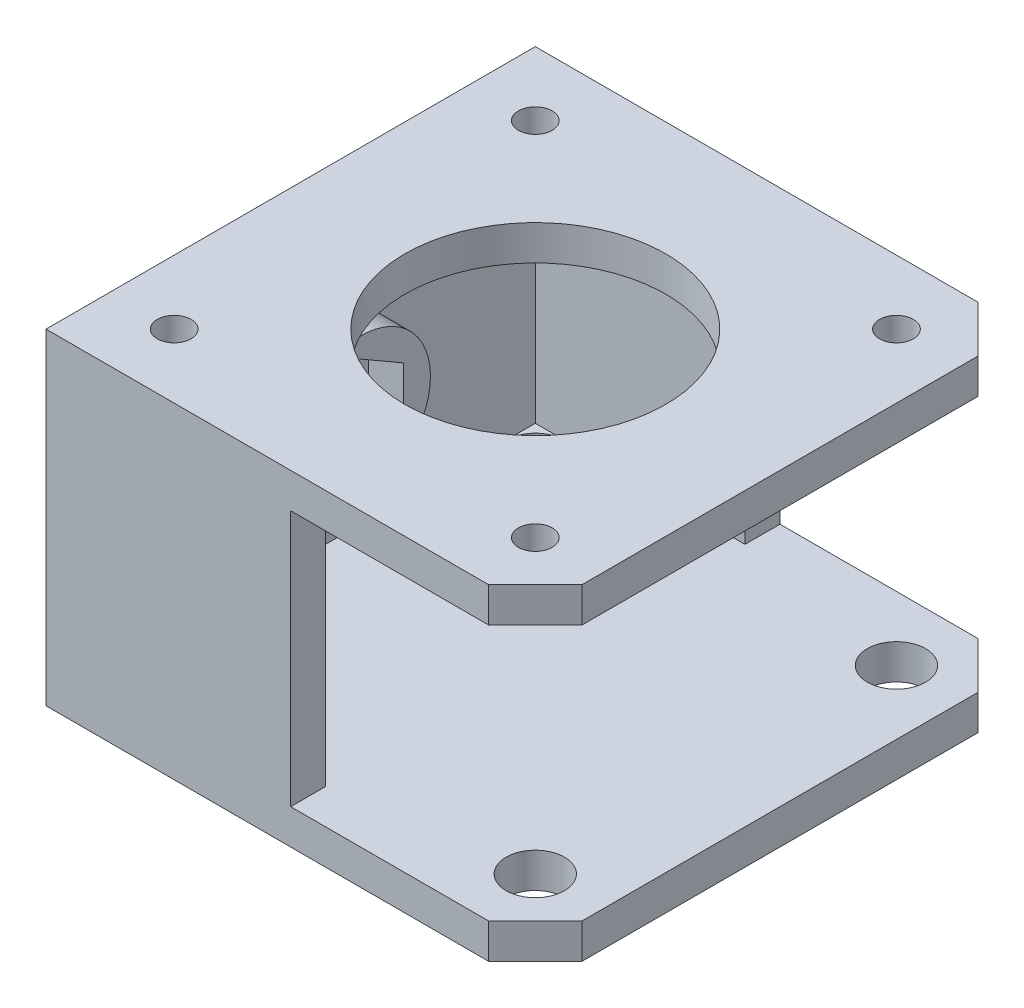
SolidWorks part; units mm, degrees
ref_plane "Front Plane" through (0, 0, 0) normal (0, 0, 1) x (1, 0, 0)
ref_plane "Top Plane" through (0, 0, 0) normal (0, 1, 0) x (1, 0, 0)
ref_plane "Right Plane" through (0, 0, 0) normal (1, 0, 0) x (0, 0, -1)
sketch "Sketch1" plane through (0, 0, 0) normal (0, 1, 0) x (1, 0, 0)
  line L0 (0, 21) -> (0, 18)
  line L1 (-21, -21) -> (21, -21)
  line L2 (-21, -21) -> (-21, 21)
  line L3 (-21, 21) -> (21, 21)
  line L4 (21, -21) -> (21, 21)
  line L5 (-21, -21) -> (21, 21) construction
  line L6 (-21, 21) -> (21, -21) construction
  line L7 (-18, -18) -> (18, -18)
  line L8 (-18, -18) -> (-18, 18)
  line L9 (-18, 18) -> (18, 18)
  line L10 (18, -18) -> (18, 18)
  line L11 (-18, -18) -> (18, 18) construction
  line L12 (-18, 18) -> (18, -18) construction
  line L13 (0, -18) -> (0, -21)
  circle A0 centre (0, 0) radius 11.2
  circle A1 centre (-15.5, 15.5) radius 1.45
  circle A2 centre (15.5, 15.5) radius 1.45
  circle A3 centre (15.5, -15.5) radius 1.45
  circle A4 centre (-15.5, -15.5) radius 1.45
  point P0 (0, 0)
  point P6 (0, 0)
  point P24 (0, 0)
  dimension "D3" = 22.4
  dimension "D4" = 2.9
  dimension "D1" = 42
  dimension "D2" = 3
  dimension "D6" = 31
  dimension "D5" = 4
extrude "Boss-Extrude1" add sketch "Sketch1" along normal blind 3 contours L1 L4 L3 L2 L10 L7 L8 L9 | L7 L10 L9 L8 A4 A3 A2 A1 A0 | L13 L7 L8 L9 L0 L3 L2 L1 region at (10.5, 0, -20.5304) region at (-0.4696, 0, -19.5) region at (9, 0, -17.4909)
extrude "Boss-Extrude2" add sketch "Sketch1<3>" against normal blind 25 contours L13 L7 L8 L9 L0 L3 L2 L1 region at (-0.4696, 0, -19.5)
sketch "Sketch1<3>" plane through (0, 0, 0) normal (0, 1, 0) x (1, 0, 0) same geometry as "Sketch1"
extrude "Boss-Extrude3" add sketch "Sketch1<4>" along normal blind 3 from surface contours L13 L7 L8 L9 L0 L3 L2 L1 | L7 L13 L1 L4 L3 L0 L9 L10 | L7 L10 L9 L8 A4 A3 A2 A1 A0 | A4 | A3 | A0 | A1 | A2 region at (10.5, 0, -20.5304) region at (-0.4696, 0, -19.5) region at (9, 0, -17.4909) region at (0, 0, 0) region at (-15.5, 0, -15.5) region at (15.5, 0, -15.5) region at (15.5, 0, 15.5) region at (-15.5, 0, 15.5) starting at face at (-9.75, -25, 0)
sketch "Sketch1<4>" plane through (0, 0, 0) normal (0, 1, 0) x (1, 0, 0) same geometry as "Sketch1"
sketch "Sketch3" plane through (-18, 0, 0) normal (1, 0, 0) x (0, 0, -1)
  line L0 (-18, -11) -> (18, -11) construction
  line L1 (-18, -22) -> (-18, 0) construction
  line L2 (18, -22) -> (18, 0) construction
  line L3 (18, -22) -> (18, 0) construction
  line L4 (0, -6.7276) -> (-3.7, -8.8638)
  line L5 (-3.7, -8.8638) -> (-3.7, -13.1362)
  line L6 (-3.7, -13.1362) -> (0, -15.2724)
  line L7 (0, -15.2724) -> (3.7, -13.1362)
  line L8 (3.7, -13.1362) -> (3.7, -8.8638)
  line L9 (3.7, -8.8638) -> (0, -6.7276)
  circle A0 centre (0, -11) radius 2.2
  circle A1 centre (0, -11) radius 3.7 construction
  circle A2 centre (0, -11) radius 6
  dimension "D1" = 4.4
  dimension "D3" = 12
  dimension "D2" = 7.4
extrude "Cut-Extrude1" cut sketch "Sketch3" against normal through all contours A0 region at (-18, -11, 0)
extrude "Boss-Extrude4" add sketch "Sketch3<3>" along normal blind 3 contours A2 L9 L8 L7 L6 L5 L4 region at (-18, -11, 5.8303)
sketch "Sketch3<3>" plane through (-18, 0, 0) normal (1, 0, 0) x (0, 0, -1) same geometry as "Sketch3"
sketch "Sketch2" plane through (0, -22, 0) normal (0, 1, 0) x (1, 0, 0)
  circle A1 centre (15.5, 15.5) radius 2.5
  circle A2 centre (15.5, -15.5) radius 2.5
  circle A3 centre (-15.5, -15.5) radius 2.5
  circle A4 centre (-15.5, 15.5) radius 2.5
  point P13 (0, 0)
  dimension "D1" = 5
  dimension "D2" = 4
extrude "Cut-Extrude2" cut sketch "Sketch2" against normal through all
chamfer "Chamfer1" distance 4 4 edges at (21, 1.5, -21) (21, -23.5, -21) (21, -23.5, 21) (21, 1.5, 21)
